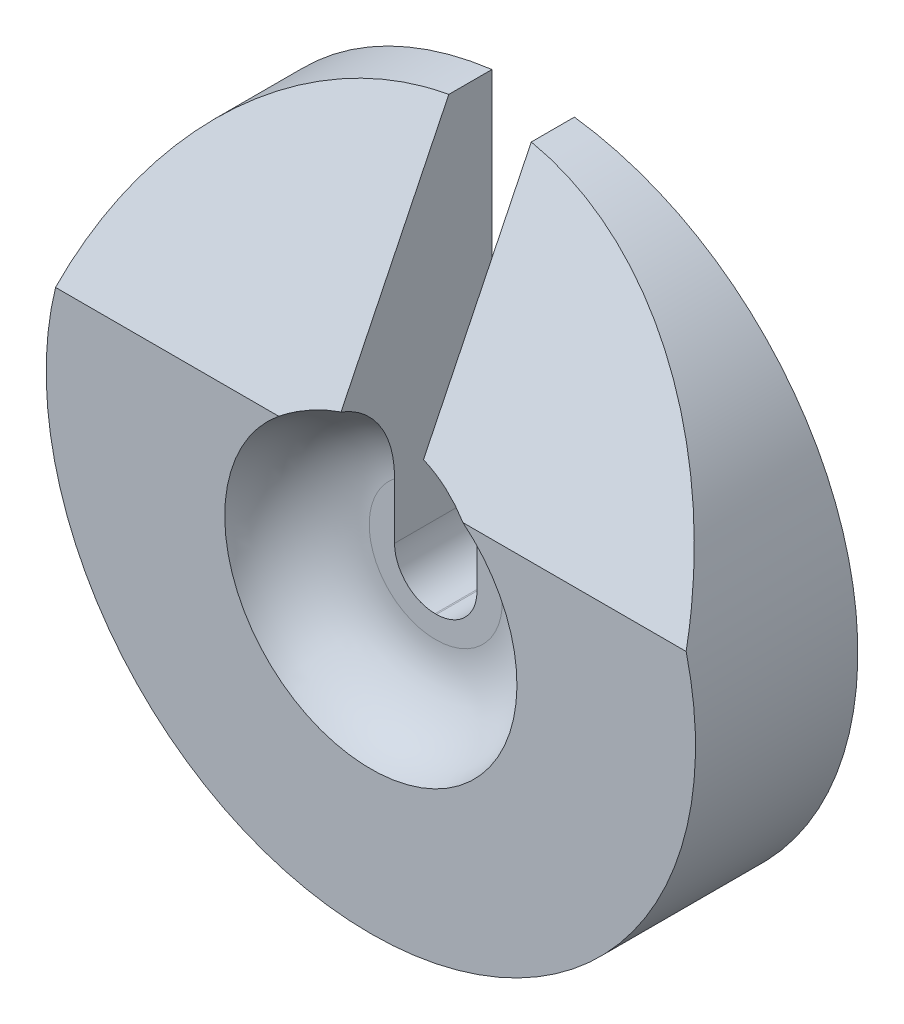
SolidWorks part; units mm, degrees
ref_plane "Спереди" through (0, 0, 0) normal (0, 0, 1) x (1, 0, 0)
ref_plane "Сверху" through (0, 0, 0) normal (0, 1, 0) x (1, 0, 0)
ref_plane "Справа" through (0, 0, 0) normal (1, 0, 0) x (0, 0, -1)
sketch "Эскиз1" plane through (0, 0, 0) normal (0, 0, 1) x (1, 0, 0)
  line L0 (0, 0) -> (0, 4.5666)
  line L1 (0.508, 4.5666) -> (-0.508, 4.5666)
  line L2 (-0.508, 4.5666) -> (-0.508, 0.5)
  line L4 (0.508, 4.5666) -> (0.508, 0.5)
  line L5 (0, 0) -> (0, -0.9882)
  line L6 (0, -0.9882) -> (-0.008, -0.9882)
  line L7 (-0.508, -0.4882) -> (-0.508, 0.5)
  line L8 (0, -0.9882) -> (0.008, -0.9882)
  line L9 (0.508, -0.4882) -> (0.508, 0.5)
  circle A0 centre (0, 0) radius 4
  arc A1 (0.508, -0.4882) -> (0.008, -0.9882) centre (0.008, -0.4882) cw
  arc A2 (-0.508, -0.4882) -> (-0.008, -0.9882) centre (-0.008, -0.4882) ccw
  dimension "D1" = 0.5
extrude "Бобышка-Вытянуть1" add sketch "Эскиз1" along normal blind 2 contours L4 L2 A0 region at (0.004, -1.1011, 0)
sketch "Эскиз2" plane through (0, 0, 2) normal (0, 0, 1) x (1, 0, 0)
  circle A0 centre (0, -0.4425) radius 1.8
  point P2 (0, 0)
  point P3 (0, -0.4425)
extrude "Вырез-Вытянуть1" cut sketch "Эскиз2" against normal blind 0.8
fillet "Скругление1" radius 1 1 edges at (0, -2.2425, 1.2)
ref_plane "Плоскость1" through (6, 0, 0) normal (1, 0, 0) x (0, 0, -1)
sketch "Эскиз3" plane through (6, 0, 0) normal (1, 0, 0) x (0, 0, -1)
  line L0 (0, 3.9676) -> (0, 0)
  line L1 (0, 0) -> (-2, 0)
  line L3 (-2, 3.9676) -> (-2, -4) construction
  line L4 (-2, 0) -> (-2, 0.9543)
  line L5 (-2, 0.9543) -> (-0.5314, 3.9676)
  line L6 (-2, 3.9676) -> (0, 3.9676) construction
  line L7 (-0.5314, 3.9676) -> (0, 3.9676)
  line L8 (-0.5314, 3.9676) -> (-2, 3.9676)
  line L9 (-2, 3.9676) -> (-2, 0.9543)
  point P8 (-1.5, 0.9543)
extrude "Вырез-Вытянуть2" cut sketch "Эскиз3" against normal blind 12.3 contours L8 L9 L5 region at (6, 2.9632, 1.5105)
